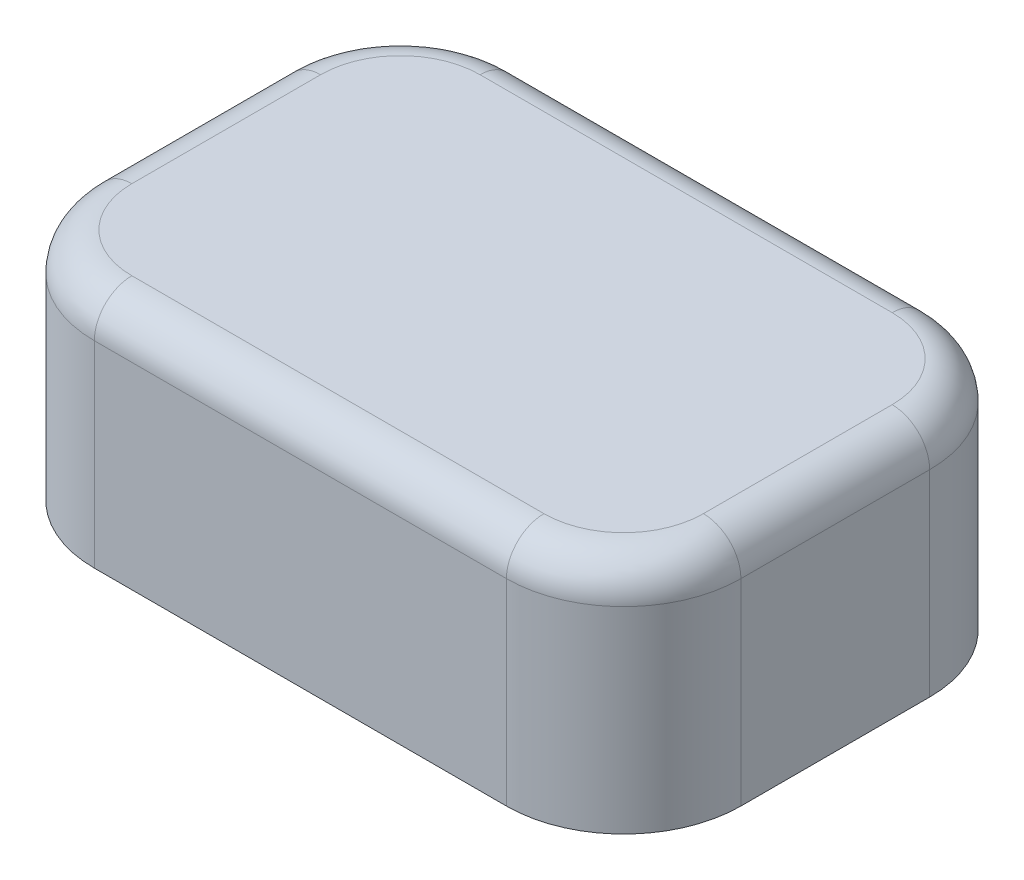
SolidWorks part; units mm, degrees
ref_plane "前视基准面" through (0, 0, 0) normal (0, 0, 1) x (1, 0, 0)
ref_plane "上视基准面" through (0, 0, 0) normal (0, 1, 0) x (1, 0, 0)
ref_plane "右视基准面" through (0, 0, 0) normal (1, 0, 0) x (0, 0, -1)
other "Configuration Table"
sketch "草图1" plane through (0, 0, 0) normal (0, 1, 0) x (1, 0, 0)
  line L0 (-2.2, 0) -> (2.2, 0) construction
  line L1 (0, 2.2) -> (0, -2.2) construction
  line L2 (2.2, 0.6) -> (2.2, -0.6)
  line L3 (-0.6, 2.2) -> (0.6, 2.2)
  line L4 (-2.2, -0.6) -> (-2.2, 0.6)
  line L5 (-0.6, -2.2) -> (0.6, -2.2)
  line L6 (-0.6, 2.2) -> (-0.6, 0.6)
  line L7 (-0.6, 0.6) -> (-2.2, 0.6)
  line L8 (-2.2, -0.6) -> (-0.6, -0.6)
  line L9 (-0.6, -0.6) -> (-0.6, -2.2)
  line L10 (0.6, -2.2) -> (0.6, -0.6)
  line L11 (0.6, -0.6) -> (2.2, -0.6)
  line L12 (2.2, 0.6) -> (0.6, 0.6)
  line L13 (0.6, 0.6) -> (0.6, 2.2)
  circle A0 centre (0, 0) radius 2.8
  point P4 (0, 0)
  point P7 (0, 0)
  point P10 (2.2, 0)
  point P13 (0, 2.2)
  point P16 (-2.2, 0)
  point P19 (0, -2.2)
  dimension "D7" = 5.6
  dimension "D1" = 4.4
  dimension "D2" = 4.4
  dimension "D3" = 1.2
  dimension "D4" = 1.2
  dimension "D5" = 1.2
  dimension "D6" = 1.2
extrude "凸台-拉伸1" add sketch "草图1" against normal blind 8
sketch "草图2" plane through (0, 0, 0) normal (0, 1, 0) x (1, 0, 0)
  line L0 (0, -9.025) -> (0, 9.025) construction
  line L1 (-13.7875, 9.025) -> (13.7875, 9.025)
  line L2 (-13.7875, -9.025) -> (13.7875, -9.025)
  line L3 (-13.7875, 9.025) -> (-13.7875, -9.025)
  line L4 (13.7875, 9.025) -> (13.7875, -9.025)
  point P4 (0, 0)
  point P8 (0, 9.025)
  point P11 (0, -9.025)
  dimension "D1" = 18.05
  dimension "D2" = 27.575
extrude "凸台-拉伸2" add sketch "草图2" along normal blind 1
sketch "草图3" plane through (0, 0, 0) normal (0, 1, 0) x (1, 0, 0)
  line L4 (13.7875, -9.025) -> (13.7875, 9.025)
  line L5 (-13.7875, -9.025) -> (13.7875, -9.025)
  line L6 (-13.7875, 9.025) -> (-13.7875, -9.025)
  line L7 (13.7875, 9.025) -> (-13.7875, 9.025)
  line L8 (13.7875, -9.025) -> (13.7875, 9.025)
  line L9 (-13.7875, -9.025) -> (13.7875, -9.025)
  line L10 (-13.7875, 9.025) -> (-13.7875, -9.025)
  line L11 (13.7875, 9.025) -> (-13.7875, 9.025)
  line L20 (12.7875, -8.025) -> (12.7875, 8.025)
  line L21 (12.7875, 8.025) -> (-12.7875, 8.025)
  line L22 (-12.7875, 8.025) -> (-12.7875, -8.025)
  line L23 (-12.7875, -8.025) -> (12.7875, -8.025)
  line L24 (12.7875, -8.025) -> (12.7875, 8.025)
  line L25 (12.7875, 8.025) -> (-12.7875, 8.025)
  line L26 (-12.7875, 8.025) -> (-12.7875, -8.025)
  line L27 (-12.7875, -8.025) -> (12.7875, -8.025)
  dimension "D1" = 0
  dimension "D2" = 1
extrude "凸台-拉伸3" add sketch "草图3" against normal blind 9
sketch "草图6" plane through (0, 0, 0) normal (0, 1, 0) x (1, 0, 0)
  line L0 (0.6, 2.2) -> (-0.6, 2.2) construction
  line L2 (2.2, -0.6) -> (2.2, 0.6) construction
  line L36 (-0.6, -2.2) -> (0.6, -2.2) construction
  line L37 (-2.2, 0.6) -> (-2.2, -0.6) construction
  line L38 (0.6, 2.2) -> (-0.6, 2.2)
  line L39 (2.2, -0.6) -> (2.2, 0.6)
  line L40 (-0.6, -2.2) -> (0.6, -2.2)
  line L41 (-2.2, 0.6) -> (-2.2, -0.6)
  line L42 (-2.2, -0.6) -> (-12.7875, -0.6)
  line L43 (-12.7875, 8.025) -> (-12.7875, -8.025) construction
  line L44 (-12.7875, -0.6) -> (-12.7875, 0.6)
  line L45 (-12.7875, 0.6) -> (-2.2, 0.6)
  line L46 (-0.6, 2.2) -> (-0.6, 8.025)
  line L47 (12.7875, 8.025) -> (-12.7875, 8.025) construction
  line L48 (-0.6, 8.025) -> (0.6, 8.025)
  line L49 (0.6, 8.025) -> (0.6, 2.2)
  line L50 (2.2, 0.6) -> (12.7875, 0.6)
  line L51 (12.7875, -8.025) -> (12.7875, 8.025) construction
  line L52 (12.7875, 0.6) -> (12.7875, -0.6)
  line L53 (12.7875, -8.025) -> (12.7875, 8.025) construction
  line L54 (12.7875, -0.6) -> (2.2, -0.6)
  line L55 (0.6, -2.2) -> (0.6, -8.025)
  line L56 (-12.7875, -8.025) -> (12.7875, -8.025) construction
  line L57 (0.6, -8.025) -> (-0.6, -8.025)
  line L58 (-12.7875, -8.025) -> (12.7875, -8.025) construction
  line L59 (-0.6, -8.025) -> (-0.6, -2.2)
  point P7 (0, 0)
  point P13 (0, 0)
extrude "凸台-拉伸4" add sketch "草图6" against normal blind 2.5
fillet "圆角1" radius 5 8 edges at (13.7875, -4, -9.025) (13.7875, -4, 9.025) (-13.7875, -4, 9.025) (-13.7875, -4, -9.025) (-12.7875, -4.5, -8.025) (12.7875, -4.5, -8.025) (12.7875, -4.5, 8.025) (-12.7875, -4.5, 8.025)
fillet "圆角2" radius 1.6 20 edges at (12.7875, 0, 1.8125) (4.1938, 0, 8.025) (-4.1937, 0, 8.025) (-12.7875, 0, 1.8125) (-12.7875, 0, -1.8125) (-4.1937, 0, -8.025) (4.1937, 0, -8.025) (12.7875, 0, -1.8125) (12.323, 1, 7.5605) (0, 1, 9.025) (-12.323, 1, 7.5605) (-13.7875, 1, 0) (-12.323, 1, -7.5605) (0, 1, -9.025) (12.323, 1, -7.5605) (13.7875, 1, 0) (11.323, 0, 6.5605) (-11.323, 0, 6.5605) (-11.323, 0, -6.5605) (11.323, 0, -6.5605)
